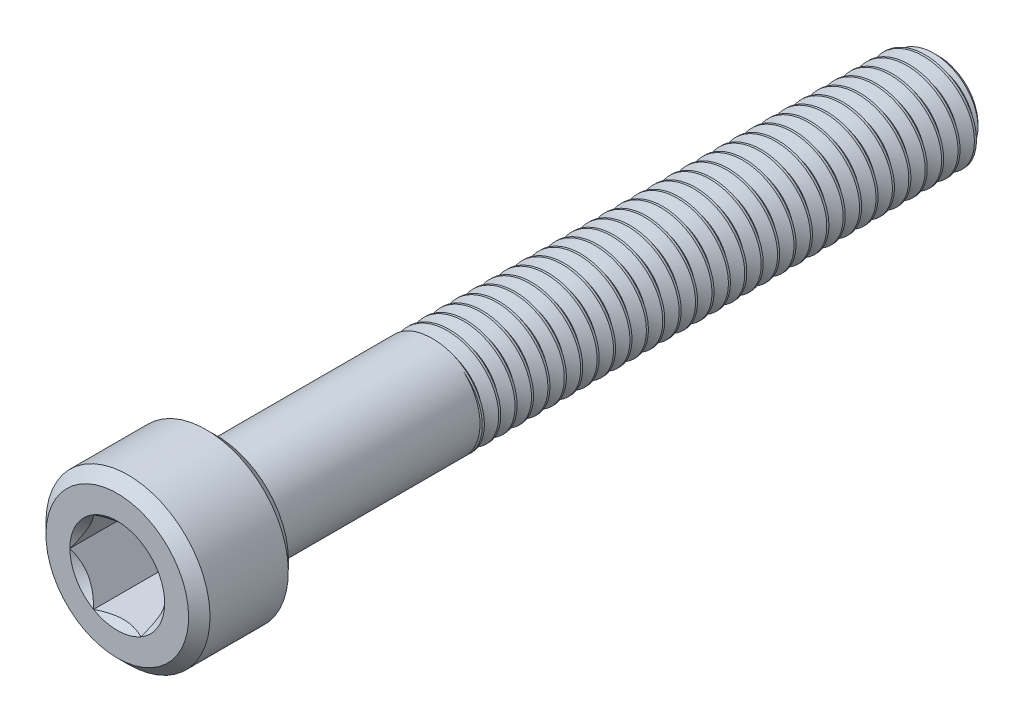
SolidWorks part; units mm, degrees
ref_plane "Front Plane" through (0, 0, 0) normal (0, 0, 1) x (1, 0, 0)
ref_plane "Top Plane" through (0, 0, 0) normal (0, 1, 0) x (1, 0, 0)
ref_plane "Right Plane" through (0, 0, 0) normal (1, 0, 0) x (0, 0, -1)
sketch "Sketch1" plane through (0, 0, 0) normal (1, 0, 0) x (0, 0, -1)
  line L0 (-10.3124, 0) -> (24.6126, 0) construction
  line L1 (-10.3124, 3.9688) -> (-10.3124, -3.9688) construction
  line L2 (24.6126, 2.413) -> (24.6126, -2.413) construction
  line L3 (24.6126, 2.413) -> (25.4063, 2.413) construction
  line L4 (-10.3124, 3.9688) -> (-15.1384, 3.9688) construction
  line L5 (-15.1384, -1.9844) -> (-15.1384, 1.9844) construction
  point P5 (0, 2.413)
  point P6 (22.6282, -2.413)
  point P9 (24.6126, 0)
  point P14 (-15.1384, 0)
  dimension "Pitch" = 0.7937
  dimension "Thread OD" = 4.826
  dimension "Thread Length" = 24.6126
  dimension "Head Dia" = 7.9375
  dimension "Head Height" = 4.826
  dimension "Length" = 34.925
  dimension "Drive Size" = 3.9688
  dimension "D1" = 1.9844
sketch "Sketch2" plane through (0, 0, 0) normal (1, 0, 0) x (0, 0, -1)
  line L0 (-15.1384, 0) -> (24.6126, 0)
  line L1 (-14.6198, 3.9688) -> (-10.831, 3.9688)
  line L2 (-15.1384, 3.4502) -> (-15.1384, 0)
  line L4 (-10.3124, 3.4502) -> (-10.3124, 2.413)
  line L5 (24.6126, 0) -> (24.6126, 1.8944)
  line L6 (24.094, 2.413) -> (-10.3124, 2.413)
  line L7 (-10.3124, 3.4502) -> (-10.831, 3.9688)
  line L8 (-15.1384, 3.4502) -> (-14.6198, 3.9688)
  line L9 (24.094, 2.413) -> (24.6126, 1.8944)
  line L10 (-10.3124, 3.9688) -> (-15.1384, 3.9688) construction
  line L11 (-10.3124, 3.9688) -> (-10.3124, -3.9688) construction
  point P0 (-12.7254, 3.9688)
  dimension "D1" = 45
  dimension "D2" = 0.5186
revolve "Revolve1" add sketch "Sketch2" angle 360 about L0
sketch "Sketch3" plane through (0, 0, 15.1384) normal (0, 0, 1) x (1, 0, 0)
  line L1 (1.1457, 1.9844) -> (-1.1457, 1.9844)
  line L2 (-1.1457, 1.9844) -> (-2.2914, 0)
  line L3 (-2.2914, 0) -> (-1.1457, -1.9844)
  line L4 (-1.1457, -1.9844) -> (1.1457, -1.9844)
  line L5 (1.1457, -1.9844) -> (2.2914, 0)
  line L6 (2.2914, 0) -> (1.1457, 1.9844)
  circle A0 centre (0, 0) radius 1.9844 construction
extrude "Cut-Extrude1" cut sketch "Sketch3" against normal blind 3.6195
sketch "Sketch4" plane through (0, 0, 15.1384) normal (0, 0, 1) x (1, 0, 0)
  circle A0 centre (0, 0) radius 2.2914
extrude "Cut-Extrude2" cut sketch "Sketch4" against normal through all draft 45
split "Split1" trim tools "Front Plane" bodies to split 106 resulting bodies 107 108
sketch "Sketch6" plane through (0, 0, -24.6126) normal (0, 0, -1) x (-1, 0, 0)
  line L0 (0, -1.9844) -> (0, 1.9844) construction
  circle A0 centre (0, 0) radius 2.413
sketch "Sketch7" plane through (0, 0, 0) normal (1, 0, 0) x (0, 0, -1)
  line L0 (24.6126, 2.413) -> (25.3071, 2.413) construction
  line L1 (25.3071, 2.413) -> (24.9599, 1.8115) construction
  line L2 (24.9599, 1.8115) -> (24.6126, 2.413) construction
  line L3 (24.6126, 2.413) -> (24.563, 2.4989) construction
  line L4 (24.563, 2.4989) -> (25.3567, 2.4989) construction
  line L5 (25.3567, 2.4989) -> (25.3071, 2.413) construction
  line L6 (24.9103, 1.8974) -> (25.0095, 1.8974) construction
  line L7 (24.9599, 2.413) -> (24.9599, 2.4989) construction
  line L8 (24.9599, 1.8974) -> (24.9599, 1.8115) construction
  line L9 (24.6126, 2.413) -> (25.4063, 2.413) construction
  dimension "D1" = 0.0992
curve "Helix/Spiral1" pitch 0.7937 height 26.2001 radius 2.413 centre (0, 0, -24.6126) axis (0, 0, 1) start towards (0, 1, 0)
sketch "Sketch8" plane through (0, 0, 0) normal (1, 0, 0) x (0, 0, -1)
  line L0 (24.5878, 2.456) -> (25.3319, 2.456)
  line L1 (24.6126, 2.413) -> (24.563, 2.4989) construction
  line L2 (25.3567, 2.4989) -> (25.3071, 2.413) construction
  line L3 (25.3319, 2.456) -> (25.0095, 1.8974)
  line L4 (25.0095, 1.8974) -> (24.9103, 1.8974)
  line L5 (24.9103, 1.8974) -> (24.5878, 2.456)
sweep "Cut-Sweep1" cut profiles "Sketch8" path "Helix/Spiral1" align with end faces yes
combine bodies "Combine1" operation type add bodies to combine 109 107
ref_axis "Axis1" through (0, 0, -24.094) along (0, 0, 1)
equation "\"D1@Cut-Extrude1\"=\"Head Height@Sketch1\"*.75"
equation "\"D2@Sketch2\"=(\"Head Dia@Sketch1\"-\"Thread OD@Sketch1\")/6"
equation "\"D3@Helix/Spiral1\"=\"Thread Length@Sketch1\"+(2*\"Pitch@Sketch1\")"
equation "\"D1@Sketch7\"=\"Pitch@Sketch1\"/8"
equation "\"D4@Helix/Spiral1\"=\"Pitch@Sketch1\""
equation "\"D1@Sketch1\"=\"Pitch@Sketch1\"*2.5"
